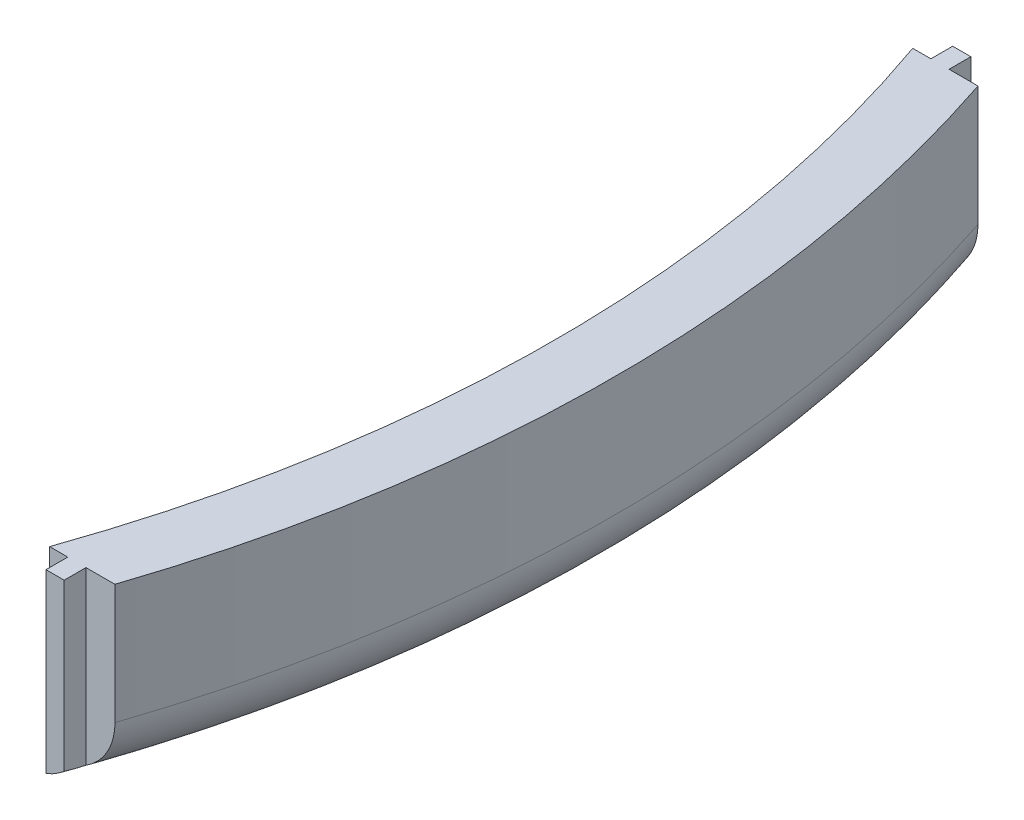
SolidWorks part; units mm, degrees
ref_plane "Front Plane" through (0, 0, 0) normal (0, 0, 1) x (1, 0, 0)
ref_plane "Top Plane" through (0, 0, 0) normal (0, 1, 0) x (1, 0, 0)
ref_plane "Right Plane" through (0, 0, 0) normal (1, 0, 0) x (0, 0, -1)
sketch "Sketch1" plane through (0, 0, 0) normal (0, 1, 0) x (1, 0, 0)
  line L0 (33.7714, 11.88) -> (34.2714, 11.88)
  line L1 (34.2714, 11.88) -> (34.2714, 12.48)
  line L2 (34.2714, 12.48) -> (34.7714, 12.48)
  line L3 (34.7714, 12.48) -> (34.7714, 11.88)
  line L4 (34.7714, 11.88) -> (35.5685, 11.88)
  line L5 (33.7714, -11.88) -> (34.2714, -11.88)
  line L6 (34.2714, -11.88) -> (34.2714, -12.48)
  line L7 (34.2714, -12.48) -> (34.7714, -12.48)
  line L8 (34.7714, -12.48) -> (34.7714, -11.88)
  line L9 (34.7714, -11.88) -> (35.5685, -11.88)
  line L10 (0, 0) -> (50000, 0) construction
  arc A0 (33.7714, -11.88) -> (33.7714, 11.88) centre (0, 0) ccw
  arc A1 (35.5685, -11.88) -> (35.5685, 11.88) centre (0, 0) ccw
  point P15 (34.5105, 9.5217)
  point P19 (33.4825, -12.6713)
  dimension "D1" = 71.6
  dimension "D2" = 75
  dimension "D3" = 23.76
  dimension "D4" = 0.5
  dimension "D5" = 0.5
  dimension "D6" = 0.6
extrude "Boss-Extrude1" add sketch "Sketch1" along normal blind 5
fillet "Fillet1" radius 1.7 1 edges at (37.5, 0, 0)
